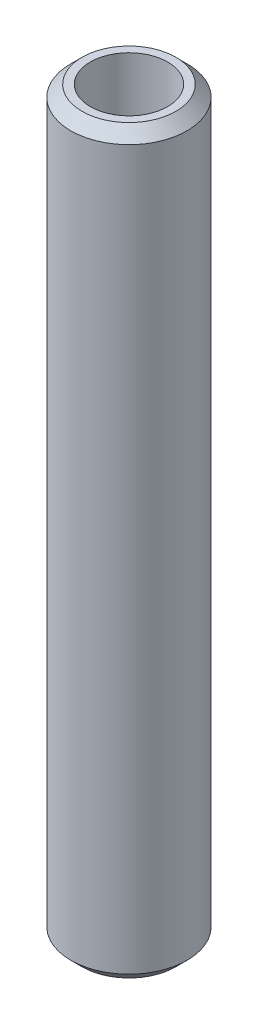
SolidWorks part; units mm, degrees
ref_plane "Front Plane" through (0, 0, 0) normal (0, 0, 1) x (1, 0, 0)
ref_plane "Top Plane" through (0, 0, 0) normal (0, 1, 0) x (1, 0, 0)
ref_plane "Right Plane" through (0, 0, 0) normal (1, 0, 0) x (0, 0, -1)
sketch "Sketch1" plane through (0, 0, 0) normal (0, 1, 0) x (1, 0, 0)
  circle A0 centre (0, 0) radius 20
  dimension "SHAFT_OD" = 40
extrude "Boss-Extrude1" add sketch "Sketch1" along normal blind 254.899
sketch "Sketch2" plane through (0, 0, 0) normal (0, 1, 0) x (1, 0, 0)
  circle A0 centre (0, 0) radius 13.3106
  dimension "BORE_D" = 26.6212
extrude "Cut-Extrude1" cut sketch "Sketch2" along normal through all
chamfer "Chamfer1" distance 3.8615 angle 45 2 edges at (0, 254.899, 20) (0, 0, 20)
